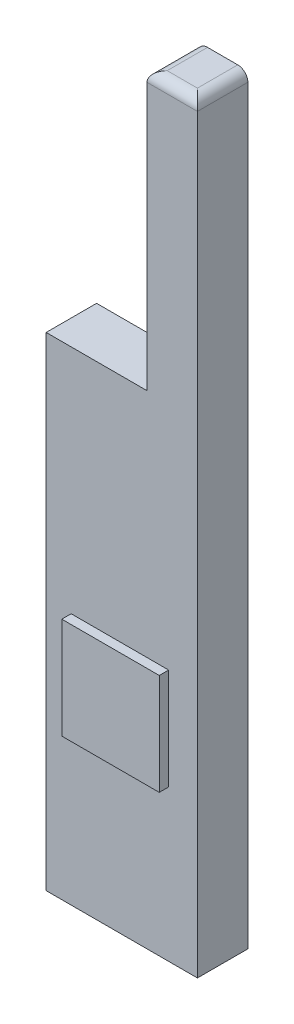
SolidWorks part; units mm, degrees
ref_plane "Front Plane" through (0, 0, 0) normal (0, 0, 1) x (1, 0, 0)
ref_plane "Top Plane" through (0, 0, 0) normal (0, 1, 0) x (1, 0, 0)
ref_plane "Right Plane" through (0, 0, 0) normal (1, 0, 0) x (0, 0, -1)
sketch "Sketch1" plane through (0, 0, 0) normal (0, 0, 1) x (1, 0, 0)
  line L0 (73.1733, 0) -> (-83.3727, 0) construction
  line L1 (10, 12) -> (10, -15.48)
  line L2 (0, 0) -> (10, 0) construction
  line L3 (0, 0) -> (0, -15.48) construction
  line L4 (0, -15.48) -> (10, -15.48) construction
  line L5 (10, 0) -> (10, -15.48) construction
  line L6 (10, -15.48) -> (0, -15.48)
  line L7 (0, -15.48) -> (0, -63.42)
  line L8 (0, -63.42) -> (15, -63.42)
  line L9 (-83.3727, -7.64) -> (73.1733, -7.64) construction
  line L10 (-83.3727, -48.42) -> (73.1733, -48.42) construction
  line L11 (15, -63.42) -> (15, 12)
  line L12 (15, 12) -> (10, 12)
  line L13 (0, -43.42) -> (15, -43.42) construction
  dimension "D1" = 10
  dimension "D2" = 15.48
  dimension "D3" = 5
  dimension "D4" = 12
  dimension "D5" = 7.64
  dimension "D6" = 40.78
  dimension "D7" = 15
  dimension "D8" = 5
extrude "Boss-Extrude1" add sketch "Sketch1" along normal blind 5
sketch "Sketch2" plane through (0, 0, 0) normal (0, 0, -1) x (-1, 0, 0)
  line L0 (-2.4798, -43.42) -> (-12.1467, -43.42) construction
  line L1 (-2.4798, -38.3985) -> (-12.1467, -38.3985)
  line L2 (-2.4798, -38.3985) -> (-2.4798, -48.4415)
  line L3 (-2.4798, -48.4415) -> (-12.1467, -48.4415)
  line L4 (-12.1467, -38.3985) -> (-12.1467, -48.4415)
  line L5 (0, -63.42) -> (-15, -63.42) construction
  dimension "D1" = 20
extrude "Boss-Extrude2" add sketch "Sketch2" against normal blind 5.93
fillet "Fillet1" radius 1 3 edges at (10, 12, 2.5) (15, 12, 2.5) (12.5, 12, 5)
sketch "Sketch3" plane through (0, -63.42, 0) normal (0, -1, 0) x (1, 0, 0)
  line L0 (15, 2.5) -> (0, 2.5) construction
  line L1 (15, 5) -> (15, 0) construction
  line L2 (0, 5) -> (0, 0) construction
  circle A0 centre (12.5, 2.5) radius 1.0294
  dimension "D1" = 2.5
extrude "Cut-Extrude1" cut sketch "Sketch3" against normal blind 0.5
